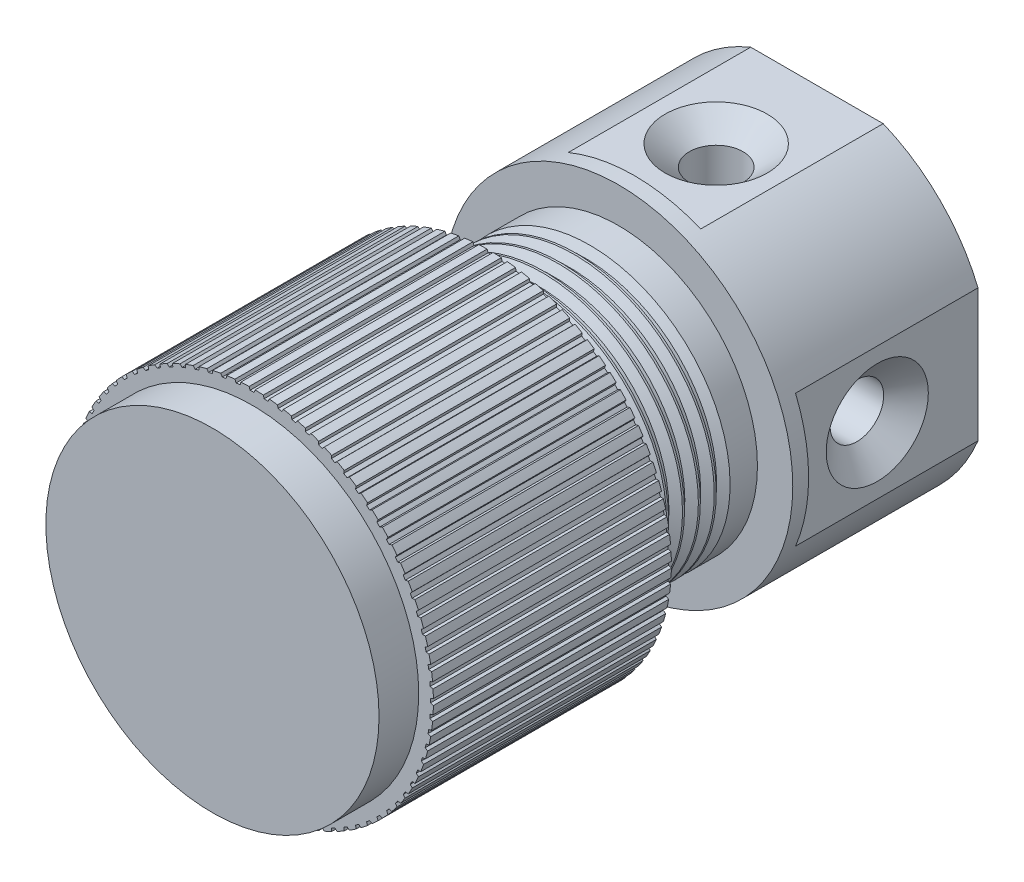
SolidWorks part; units mm, degrees
material "AISI 316 Stainless Steel Sheet (SS)"
ref_plane "Front Plane" through (0, 0, 0) normal (0, 0, 1) x (1, 0, 0)
ref_plane "Top Plane" through (0, 0, 0) normal (0, 1, 0) x (1, 0, 0)
ref_plane "Right Plane" through (0, 0, 0) normal (1, 0, 0) x (0, 0, -1)
sketch "Sketch1" plane through (0, 0, 0) normal (0, 0, 1) x (1, 0, 0)
  circle A0 centre (0, 0) radius 21.95
  dimension "D1" = 43.9
extrude "Boss-Extrude1" add sketch "Sketch1" along normal blind 25
sketch "Sketch2" plane through (0, 0, 0) normal (0, 0, -1) x (-1, 0, 0)
  line L1 (-20.3, 30.7063) -> (-37.2044, 30.7063)
  line L2 (-20.3, 30.7063) -> (-20.3, -29.7817)
  line L3 (-20.3, -29.7817) -> (-37.2044, -29.7817)
  line L4 (-37.2044, 30.7063) -> (-37.2044, -29.7817)
  line L5 (20.3, 30.7063) -> (32.4896, 30.7063)
  line L6 (20.3, 30.7063) -> (20.3, -35.5315)
  line L7 (20.3, -35.5315) -> (32.4896, -35.5315)
  line L8 (32.4896, 30.7063) -> (32.4896, -35.5315)
  line L9 (-27.5604, 39.3894) -> (29.5928, 39.3894)
  line L10 (-27.5604, 39.3894) -> (-27.5604, 20.3)
  line L11 (-27.5604, 20.3) -> (29.5928, 20.3)
  line L12 (29.5928, 39.3894) -> (29.5928, 20.3)
  line L13 (33.8476, -20.3) -> (-35.4951, -20.3)
  line L14 (33.8476, -20.3) -> (33.8476, -38.4694)
  line L15 (33.8476, -38.4694) -> (-35.4951, -38.4694)
  line L16 (-35.4951, -20.3) -> (-35.4951, -38.4694)
  circle M14 centre (0, 0) radius 21.95
  dimension "D1" = 20.3
  dimension "D2" = 20.3
  dimension "D3" = 20.3
  dimension "D4" = 20.3
extrude "Cut-Extrude1" cut sketch "Sketch2" against normal blind 23 contours L2 M14 | L11 M14 | L6 M14 | L13 M14 region at (20.9622, 0, 0) region at (0, 20.9622, 0) region at (0, -20.9622, 0) region at (-20.9622, 0, 0)
sketch "Sketch3" plane through (20.3, 0, 0) normal (1, 0, 0) x (0, 0, -1)
  line L0 (-12.7, 36.1341) -> (-12.7, -42.2473) construction
  line L1 (0, 8.3494) -> (0, -8.3494) construction
  dimension "D1" = 12.7
hole_wizard "CSK for 1/4 Flat Head Machine Screw (100)1" positions "Sketch4" profile "Sketch5" countersink size "1/4" standard "ANSI Inch"
sketch "Sketch4" plane through (20.3, 0, 0) normal (1, 0, 0) x (0, 0, -1)
  line L0 (-12.7, 36.1341) -> (-12.7, -42.2473) construction
  point P0 (-12.7, 0)
sketch "Sketch5" plane through (20.3, 0, 12.7) normal (0, 1, 0) x (0, 0, -1)
  line L0 (0, 0) -> (0, 12.0298)
  line L1 (0, 12.0298) -> (3.3782, 10)
  line L2 (3.3782, 10) -> (3.3782, 2.5682)
  line L3 (3.3782, 2.5682) -> (6.4389, 0)
  line L5 (6.4389, 0) -> (0, 0)
  line L6 (-3.3782, 2.5682) -> (-6.4389, 0) construction
  line L10 (0, 12.0298) -> (-3.3782, 10) construction
  line L11 (0, -6.35) -> (0, 107.95) construction
  dimension "Hole Dia." = 6.7564
  dimension "Hole Depth" = 10
  dimension "Near C'Sink Dia." = 12.8778
  dimension "Near C'Sink Angle" = 100
  dimension "Drill Angle" = 118
hole_wizard "CSK for 1/4 Flat Head Machine Screw (100)2" positions "Sketch6" profile "Sketch7" countersink size "1/4" standard "ANSI Inch"
sketch "Sketch6" plane through (-20.3, 0, 0) normal (-1, 0, 0) x (0, 0, 1)
  line L0 (12.7, 36.1341) -> (12.7, -42.2473) construction
  point P0 (12.7, 0)
sketch "Sketch7" plane through (-20.3, 0, 12.7) normal (0, 1, 0) x (0, 0, 1)
  line L0 (0, 0) -> (0, 12.0298)
  line L1 (0, 12.0298) -> (3.3782, 10)
  line L2 (3.3782, 10) -> (3.3782, 2.5682)
  line L3 (3.3782, 2.5682) -> (6.4389, 0)
  line L5 (6.4389, 0) -> (0, 0)
  line L6 (-3.3782, 2.5682) -> (-6.4389, 0) construction
  line L10 (0, 12.0298) -> (-3.3782, 10) construction
  line L11 (0, -6.35) -> (0, 107.95) construction
  dimension "Hole Dia." = 6.7564
  dimension "Hole Depth" = 10
  dimension "Near C'Sink Dia." = 12.8778
  dimension "Near C'Sink Angle" = 100
  dimension "Drill Angle" = 118
sketch "Sketch8" plane through (0, 20.3, 0) normal (0, 1, 0) x (1, 0, 0)
  line L0 (-36.0489, -12.7) -> (48.2644, -12.7) construction
  line L1 (8.3494, 0) -> (-8.3494, 0) construction
  dimension "D1" = 12.7
hole_wizard "CSK for 1/4 Flat Head Machine Screw (100)3" positions "Sketch9" profile "Sketch10" countersink size "1/4" standard "ANSI Inch"
sketch "Sketch9" plane through (0, 20.3, 0) normal (0, 1, 0) x (1, 0, 0)
  line L0 (-36.0489, -12.7) -> (48.2644, -12.7) construction
  point P0 (0, -12.7)
  point P4 (0, -12.7)
sketch "Sketch10" plane through (0, 20.3, 12.7) normal (1, 0, 0) x (0, 0, 1)
  line L0 (0, 0) -> (0, 12.0298)
  line L1 (0, 12.0298) -> (3.3782, 10)
  line L2 (3.3782, 10) -> (3.3782, 2.5682)
  line L3 (3.3782, 2.5682) -> (6.4389, 0)
  line L5 (6.4389, 0) -> (0, 0)
  line L6 (-3.3782, 2.5682) -> (-6.4389, 0) construction
  line L10 (0, 12.0298) -> (-3.3782, 10) construction
  line L11 (0, -6.35) -> (0, 107.95) construction
  dimension "Hole Dia." = 6.7564
  dimension "Hole Depth" = 10
  dimension "Near C'Sink Dia." = 12.8778
  dimension "Near C'Sink Angle" = 100
  dimension "Drill Angle" = 118
hole_wizard "CSK for 1/4 Flat Head Machine Screw (100)4" positions "Sketch11" profile "Sketch12" countersink size "1/4" standard "ANSI Inch"
sketch "Sketch11" plane through (0, -20.3, 0) normal (0, -1, 0) x (-1, 0, 0)
  line L0 (36.0489, -12.7) -> (-48.2644, -12.7) construction
  point P0 (0, -12.7)
sketch "Sketch12" plane through (0, -20.3, 12.7) normal (1, 0, 0) x (0, 0, -1)
  line L0 (0, 0) -> (0, 12.0298)
  line L1 (0, 12.0298) -> (3.3782, 10)
  line L2 (3.3782, 10) -> (3.3782, 2.5682)
  line L3 (3.3782, 2.5682) -> (6.4389, 0)
  line L5 (6.4389, 0) -> (0, 0)
  line L6 (-3.3782, 2.5682) -> (-6.4389, 0) construction
  line L10 (0, 12.0298) -> (-3.3782, 10) construction
  line L11 (0, -6.35) -> (0, 107.95) construction
  dimension "Hole Dia." = 6.7564
  dimension "Hole Depth" = 10
  dimension "Near C'Sink Dia." = 12.8778
  dimension "Near C'Sink Angle" = 100
  dimension "Drill Angle" = 118
sketch "Sketch13" plane through (0, 0, 25) normal (0, 0, 1) x (1, 0, 0)
  circle A0 centre (0, 0) radius 17.5
  dimension "D1" = 35
extrude "Boss-Extrude2" add sketch "Sketch13" along normal blind 51.2
sketch "Sketch14" plane through (0, 0, 76.2) normal (0, 0, 1) x (1, 0, 0)
  circle A0 centre (0, 0) radius 22.85
  dimension "D1" = 45.7
extrude "Boss-Extrude3" add sketch "Sketch14" against normal blind 35
sketch "Sketch16" plane through (0, 0, 76.2) normal (0, 0, 1) x (1, 0, 0)
  circle A0 centre (0, 0) radius 22.85
  circle A1 centre (0, 0) radius 21
  dimension "D1" = 42
extrude "Cut-Extrude2" cut sketch "Sketch16" against normal blind 5
thread "Thread1" pitch 2 method cut profile "Thread Profile1" start angle 0, offset 0, length 12, pitch 2, diameter 35
ref_plane "Plane1" through (-17.5, 0, 41.2) normal (0, -1, 0) x (-1, 0, 0)
sketch "Thread Profile1" plane through (-17.5, 0, 41.2) normal (0, -1, 0) x (-1, 0, 0)
  line L0 (0, 0) -> (0, 2) construction
  line L11 (0, 0) -> (0, 1.75)
  line L12 (0, 1.75) -> (-1.0825, 1.125)
  line L13 (-1.0825, 1.125) -> (-1.0825, 0.625)
  line L15 (-1.0825, 0.625) -> (0, 0)
  line L17 (-1.0825, 0.875) -> (0, 0.875) construction
  point P2 (0, 0)
  dimension "Pitch" = 2
  dimension "Profile_Angle" = 60
  dimension "Profile_Land" = 0.5
  dimension "Profile_Height" = 1.0825
sketch "Sketch17" plane through (0, 0, 71.2) normal (0, 0, 1) x (1, 0, 0)
  line L0 (0, 0) -> (0, 29.2273) construction
  line L1 (0.3763, 22.8469) -> (0.25, 22.5)
  line L2 (0.25, 22.5) -> (-0.25, 22.5)
  line L3 (-0.25, 22.5) -> (-0.3763, 22.8469)
  circle A0 centre (0, 0) radius 22.85
  circle A1 centre (0, 0) radius 22.85 construction
  circle M7 centre (0, 0) radius 22.85
  dimension "D1" = 20
  dimension "D2" = 0.5
  dimension "D3" = 22.5
extrude "Cut-Extrude3" cut sketch "Sketch17" against normal up to surface (30 mm away) contours L2 L0 A0 L3 | L0 L2 L1 M7 region at (-0.1586, 22.6863, 71.2) region at (0.1586, 22.6863, 71.2) up to face at (17.5, 0, 41.2)
pattern_circular "CirPattern1" count 80 over 360 of "Cut-Extrude3"
